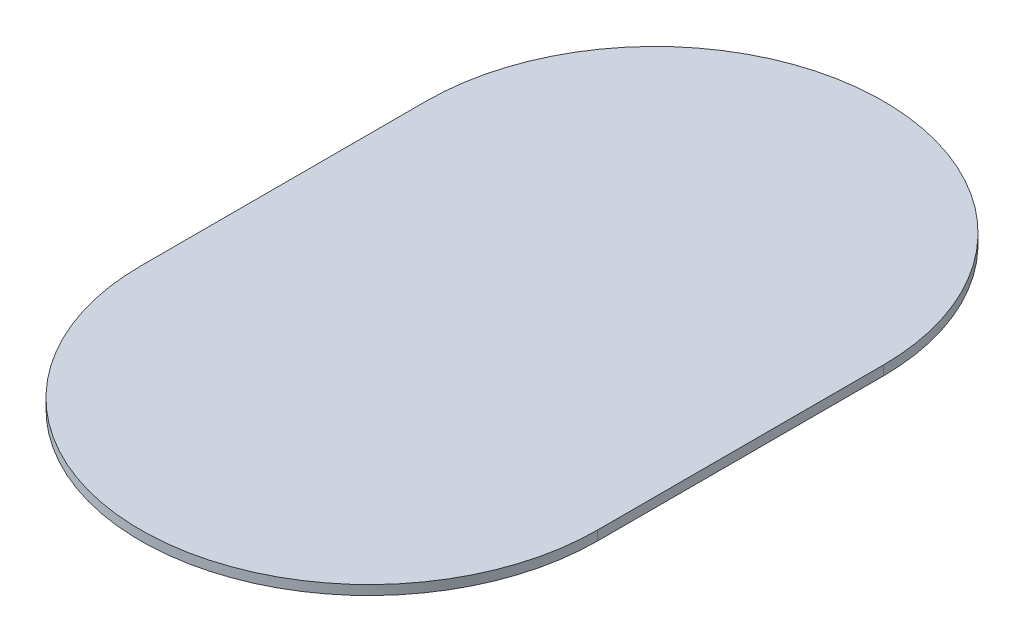
SolidWorks part; units mm, degrees
ref_plane "Front Plane" through (0, 0, 0) normal (0, 0, 1) x (1, 0, 0)
ref_plane "Top Plane" through (0, 0, 0) normal (0, 1, 0) x (1, 0, 0)
ref_plane "Right Plane" through (0, 0, 0) normal (1, 0, 0) x (0, 0, -1)
sketch "Sketch1" plane through (0, 0, 0) normal (0, 1, 0) x (1, 0, 0)
  line L0 (-351.0137, 141.7364) -> (-351.0137, -58.2636) construction
  line L5 (-413.5137, 4.2364) -> (-413.5137, 79.2364)
  line L6 (-288.5137, 4.2364) -> (-288.5137, 79.2364)
  line L7 (-351.0137, 41.7364) -> (-413.5137, 41.7364) construction
  line L8 (0, 100) -> (0, 37.5) construction
  line L10 (-62.5, -37.5) -> (-62.5, 37.5) construction
  line L12 (62.5, -37.5) -> (62.5, 37.5) construction
  line L13 (-60, -37.5) -> (-60, 37.5)
  line L14 (60, -37.5) -> (60, 37.5)
  line L15 (0, 0) -> (62.5, 0) construction
  arc A4 (-288.5137, 79.2364) -> (-413.5137, 79.2364) centre (-351.0137, 79.2364) ccw
  arc A5 (-288.5137, 4.2364) -> (-413.5137, 4.2364) centre (-351.0137, 4.2364) cw
  arc A7 (62.5, 37.5) -> (-62.5, 37.5) centre (0, 37.5) ccw construction
  arc A8 (62.5, -37.5) -> (-62.5, -37.5) centre (0, -37.5) cw construction
  arc A9 (60, 37.5) -> (-60, 37.5) centre (0, 37.5) ccw
  arc A10 (60, -37.5) -> (-60, -37.5) centre (0, -37.5) cw
  point P0 (-351.7759, 40.949)
  point P1 (-351.0008, 41.7946)
  point P2 (-351.0137, 41.7364)
  point P13 (0, 0)
  point P14 (-62.5, 0)
  dimension "D1" = 62.5
  dimension "D9" = 62.5
  dimension "D2" = 200
  dimension "D3" = 37.5
  dimension "D4" = 125
  dimension "D5" = 100
  dimension "D6" = 62.5
  dimension "D7" = 100
  dimension "D8" = 37.5
  dimension "D10" = 62.5
  dimension "D11" = 75
  dimension "D12" = 62.5
  dimension "D14" = 62.5
  dimension "D15" = 2.5
extrude "Boss-Extrude1" add sketch "Sketch1" along normal blind 2.5 contours A9 L13 A10 L14
